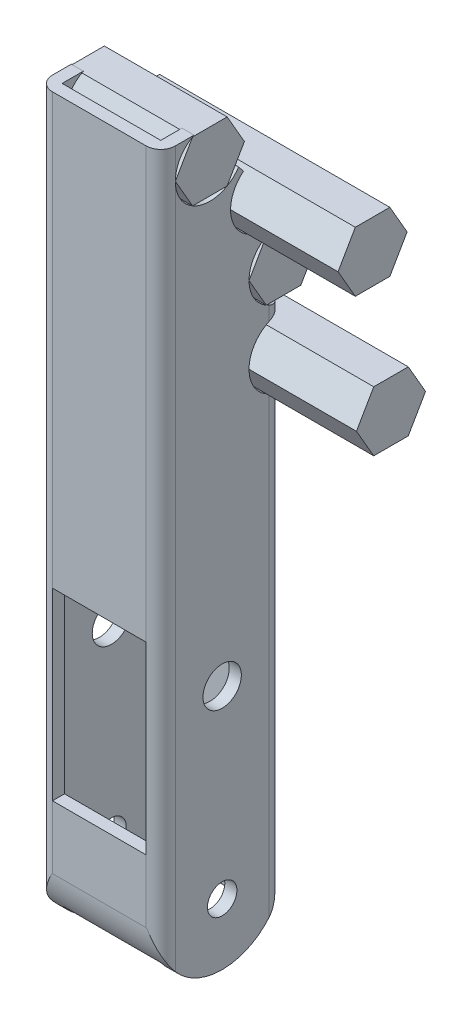
SolidWorks part; units mm, degrees
material "6061-T6 (SS)"
ref_plane "Front Plane" through (0, 0, 0) normal (0, 0, 1) x (1, 0, 0)
ref_plane "Top Plane" through (0, 0, 0) normal (0, 1, 0) x (1, 0, 0)
ref_plane "Right Plane" through (0, 0, 0) normal (1, 0, 0) x (0, 0, -1)
sketch "Sketch1" plane through (0, 0, 0) normal (0, 1, 0) x (1, 0, 0)
  line L1 (0, 0) -> (25.4, 0)
  line L2 (0, 0) -> (0, 25.4)
  line L3 (0, 25.4) -> (25.4, 25.4)
  line L4 (25.4, 0) -> (25.4, 25.4)
  line L5 (2.5, 22.9) -> (22.9, 22.9)
  line L6 (2.5, 22.9) -> (2.5, 2.5)
  line L7 (2.5, 2.5) -> (22.9, 2.5)
  line L8 (22.9, 22.9) -> (22.9, 2.5)
  dimension "D1" = 25.4
  dimension "D2" = 25.4
  dimension "D3" = 2.5
  dimension "D4" = 2.5
  dimension "D5" = 2.5
  dimension "D6" = 2.5
extrude "Boss-Extrude1" add sketch "Sketch1" along normal blind 152.4
sketch "Sketch2" plane through (0, 0, 0) normal (-1, 0, 0) x (0, 0, 1)
  line L2 (-25.4, 13.0422) -> (-33.0886, 13.0422)
  line L4 (-33.0886, 13.0422) -> (-33.0886, -7.6856)
  line L5 (-25.4, 152.4) -> (-25.4, 0) construction
  line L6 (-33.0886, -7.6856) -> (17.8386, -8.8295)
  line L7 (17.8386, -8.8295) -> (0.0046, 12.7)
  arc A0 (-25.4, 13.0422) -> (0.0046, 12.7) centre (-12.7, 12.7) ccw
  circle A1 centre (-12.7, 12.7) radius 3.048
  dimension "D1" = 6.096
extrude "Cut-Extrude1" cut sketch "Sketch2" against normal blind 203.2
fillet "Fillet1" radius 3 4 edges at (25.4, 82.3789, -25.4) (25.4, 82.3789, 0) (0, 82.3789, 0) (0, 82.3789, -25.4)
sketch "Sketch15" plane through (0, 0, 0) normal (-1, 0, 0) x (0, 0, 1)
  line L0 (-12.7, 12.7) -> (-12.7, 50.8) construction
  circle A0 centre (-12.7, 12.7) radius 3.048 construction
  circle A1 centre (-12.7, 12.7) radius 3.048 construction
  circle A2 centre (-12.7, 50.8) radius 3.97
extrude "Cut-Extrude9" cut sketch "Sketch15" against normal through all contours A2
sketch "Sketch16" plane through (0, 0, 0) normal (0, 0, 1) x (1, 0, 0)
  line L0 (0, 54.77) -> (0, 46.83) construction
  line L1 (0, 54.77) -> (0, 46.83) construction
  line L2 (0, 50.8) -> (22.4, 50.8) construction
  line L3 (12.7, 12.3578) -> (12.7, 152.4) construction
  line L4 (3, 12.3578) -> (22.4, 12.3578)
  line L5 (22.4, 12.3578) -> (22.4, 152.4)
  line L6 (22.4, 152.4) -> (3, 152.4)
  line L7 (3, 152.4) -> (3, 12.3578)
  line L8 (3, 12.3578) -> (22.4, 12.3578) construction
  line L9 (22.4, 12.3578) -> (22.4, 152.4) construction
  line L10 (22.4, 152.4) -> (3, 152.4) construction
  line L11 (3, 152.4) -> (3, 12.3578) construction
  line L12 (3, 63.5) -> (22.4, 63.5)
  line L13 (22.4, 63.5) -> (22.4, 38.1)
  line L15 (3, 38.1) -> (3, 63.5)
  line L18 (3, 38.1) -> (3, 25.4)
  line L19 (3, 25.4) -> (22.4, 25.4)
  line L20 (22.4, 38.1) -> (22.4, 25.4)
  point P14 (3, 50.8)
  dimension "D2" = 12.7
  dimension "D3" = 19.4
  dimension "D1" = 0
extrude "Cut-Extrude10" cut sketch "Sketch16" against normal blind 10
sketch "Sketch17" plane through (0, 0, 0) normal (-1, 0, 0) x (0, 0, 1)
  line L0 (-25.4, 12.3578) -> (-25.4, 152.4) construction
  line L15 (-16.1024, 142.085) -> (-17.1156, 140.8239)
  line L16 (-24.0783, 128.5586) -> (-24.2224, 127.696)
  line L17 (-25.4, 113.5063) -> (-25.4, 111.9188)
  line L18 (-25.4, 97.6312) -> (-53.1049, 97.6312)
  line L19 (-53.1049, 97.6312) -> (-53.1049, 163.8699)
  line L20 (-53.1049, 163.8699) -> (2.5527, 163.8699)
  line L21 (2.5527, 163.8699) -> (-6.9522, 152.433)
  circle A0 centre (-10.16, 146.05) radius 7.1437
  circle A8 centre (-21.59, 135.255) radius 7.1437
  circle A9 centre (-25.4, 120.65) radius 7.1438
  circle A10 centre (-25.4, 104.775) radius 7.1438
  circle A11 centre (-12.7, 12.7) radius 3.048 construction
  line M17 (-3, 152.4) -> (-22.4, 152.4)
  line M18 (-22.4, 152.4) -> (-22.4, 4.4953)
  dimension "D2" = 133.35
  dimension "D1" = 14.2875
  dimension "D4" = 92.075
  dimension "D3" = 15.24
  dimension "D5" = 0
  dimension "D6" = 0
  dimension "D7" = 3.81
  dimension "D8" = 107.95
  dimension "D9" = 122.555
extrude "Cut-Extrude11" cut sketch "Sketch17" against normal through all contours A10 L17 A9 L16 A8 A0 L21 L20 L19 L18 M18 M17 | A8 L15 A0 M17 M18 | A9 | A10 | A8 | A0 region at (0, 147.4383, -19.2844) region at (0, 136.2027, -36.6157)
sketch "Sketch19" plane through (0, 0, 0) normal (-1, 0, 0) x (0, 0, 1)
  line L0 (-27.6084, 116.9806) -> (-30.6752, 116.1589)
  line L1 (-2.9127, 159.7549) -> (-3.7345, 162.8217)
  line L2 (-31.9735, 126.0199) -> (6.1265, 126.0199) construction
  arc A0 (-3.7345, 162.8217) -> (-30.6752, 116.1589) centre (6.1265, 126.0199) ccw
  arc A1 (-2.9127, 159.7549) -> (-27.6084, 116.9806) centre (6.1265, 126.0199) ccw
  dimension "D1" = 76.2
  dimension "D2" = 15
  dimension "D3" = 69.85
sketch "Sketch21" plane through (0, 0, 0) normal (-1, 0, 0) x (0, 0, 1)
  line L1 (-28.9719, 110.9617) -> (-32.5437, 104.775)
  line L2 (-32.5437, 104.775) -> (-28.9719, 98.5883)
  line L3 (-28.9719, 98.5883) -> (-21.8281, 98.5883)
  line L4 (-21.8281, 98.5883) -> (-18.2562, 104.775)
  line L5 (-18.2562, 104.775) -> (-21.8281, 110.9617)
  line L6 (-21.8281, 110.9617) -> (-28.9719, 110.9617)
  line L7 (-18.2562, 120.65) -> (-21.8281, 126.8367)
  line L8 (-21.8281, 126.8367) -> (-28.9719, 126.8367)
  line L9 (-28.9719, 126.8367) -> (-32.5437, 120.65)
  line L10 (-32.5437, 120.65) -> (-28.9719, 114.4633)
  line L11 (-28.9719, 114.4633) -> (-21.8281, 114.4633)
  line L12 (-21.8281, 114.4633) -> (-18.2562, 120.65)
  line L13 (-18.0181, 141.4417) -> (-25.1619, 141.4417)
  line L14 (-25.1619, 141.4417) -> (-28.7337, 135.255)
  line L15 (-28.7337, 135.255) -> (-25.1619, 129.0683)
  line L16 (-25.1619, 129.0683) -> (-18.0181, 129.0683)
  line L17 (-18.0181, 129.0683) -> (-14.4462, 135.255)
  line L18 (-14.4462, 135.255) -> (-18.0181, 141.4417)
  line L19 (-3.0162, 146.05) -> (-6.5881, 152.2367)
  line L20 (-6.5881, 152.2367) -> (-13.7319, 152.2367)
  line L21 (-13.7319, 152.2367) -> (-17.3037, 146.05)
  line L22 (-17.3037, 146.05) -> (-13.7319, 139.8633)
  line L23 (-13.7319, 139.8633) -> (-6.5881, 139.8633)
  line L24 (-6.5881, 139.8633) -> (-3.0162, 146.05)
  circle A1 centre (-25.4, 104.775) radius 6.1867 construction
  circle A2 centre (-25.4, 120.65) radius 6.1867 construction
  circle A3 centre (-21.59, 135.255) radius 6.1867 construction
  circle A4 centre (-10.16, 146.05) radius 6.1867 construction
extrude "Boss-Extrude2" add sketch "Sketch21" against normal up to surface (25.4 mm away) separate body up to face at (25.4, 50.8, -8.73)
sketch "Sketch22" plane through (25.4, 0, 0) normal (1, 0, 0) x (0, 0, -1)
  line L6 (18.0181, 141.4417) -> (14.4462, 135.255)
  line L7 (14.4462, 135.255) -> (18.0181, 129.0683)
  line L8 (18.0181, 129.0683) -> (25.1619, 129.0683)
  line L9 (25.1619, 129.0683) -> (28.7337, 135.255)
  line L10 (28.7337, 135.255) -> (25.1619, 141.4417)
  line L11 (25.1619, 141.4417) -> (18.0181, 141.4417)
  line L12 (18.0181, 141.4417) -> (14.4462, 135.255)
  line L13 (14.4462, 135.255) -> (18.0181, 129.0683)
  line L14 (18.0181, 129.0683) -> (25.1619, 129.0683)
  line L15 (25.1619, 129.0683) -> (28.7337, 135.255)
  line L16 (28.7337, 135.255) -> (25.1619, 141.4417)
  line L17 (25.1619, 141.4417) -> (18.0181, 141.4417)
  line L18 (28.9719, 110.9617) -> (21.8281, 110.9617)
  line L19 (21.8281, 110.9617) -> (18.2562, 104.775)
  line L20 (18.2562, 104.775) -> (21.8281, 98.5883)
  line L21 (21.8281, 98.5883) -> (28.9719, 98.5883)
  line L22 (28.9719, 98.5883) -> (32.5437, 104.775)
  line L23 (32.5437, 104.775) -> (28.9719, 110.9617)
  line L24 (28.9719, 110.9617) -> (21.8281, 110.9617)
  line L25 (21.8281, 110.9617) -> (18.2562, 104.775)
  line L26 (18.2562, 104.775) -> (21.8281, 98.5883)
  line L27 (21.8281, 98.5883) -> (28.9719, 98.5883)
  line L28 (28.9719, 98.5883) -> (32.5437, 104.775)
  line L29 (32.5437, 104.775) -> (28.9719, 110.9617)
  dimension "D1" = 0
  dimension "D2" = 0
extrude "Boss-Extrude3" add sketch "Sketch22" along normal blind 22.225
